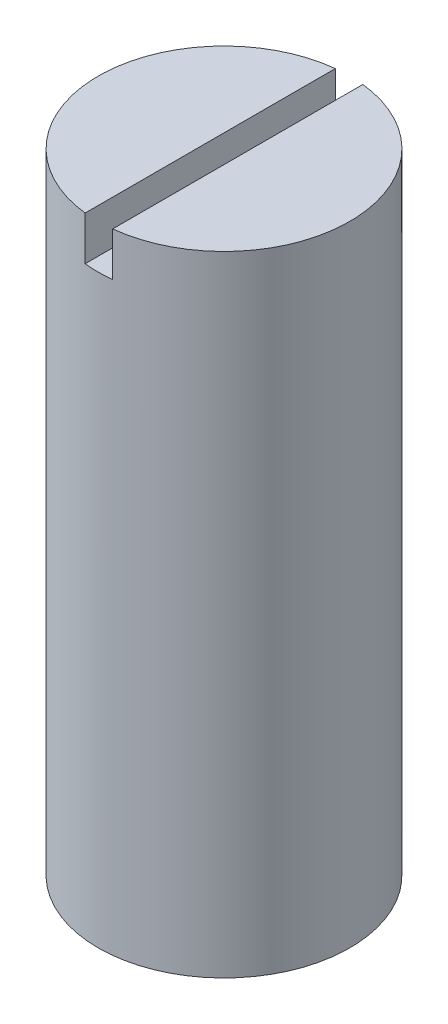
SolidWorks part; units mm, degrees
material "Gray Cast Iron"
ref_plane "Front Plane" through (0, 0, 0) normal (0, 0, 1) x (1, 0, 0)
ref_plane "Top Plane" through (0, 0, 0) normal (0, 1, 0) x (1, 0, 0)
ref_plane "Right Plane" through (0, 0, 0) normal (1, 0, 0) x (0, 0, -1)
sketch "Sketch1" plane through (0, 0, 0) normal (0, 1, 0) x (1, 0, 0)
  circle A0 centre (0, 0) radius 16
  dimension "D1" = 32
extrude "Boss-Extrude1" add sketch "Sketch1" along normal blind 80
sketch "Sketch2" plane through (0, 0, 0) normal (0, 0, 1) x (1, 0, 0)
  line L0 (-1.75, 74.4125) -> (1.75, 74.4125)
  line L1 (1.75, 74.4125) -> (1.75, 82)
  line L2 (1.75, 82) -> (-1.75, 82)
  line L3 (-1.75, 82) -> (-1.75, 74.4125)
extrude "Cut-Extrude1" cut sketch "Sketch2" against normal mid plane 36
